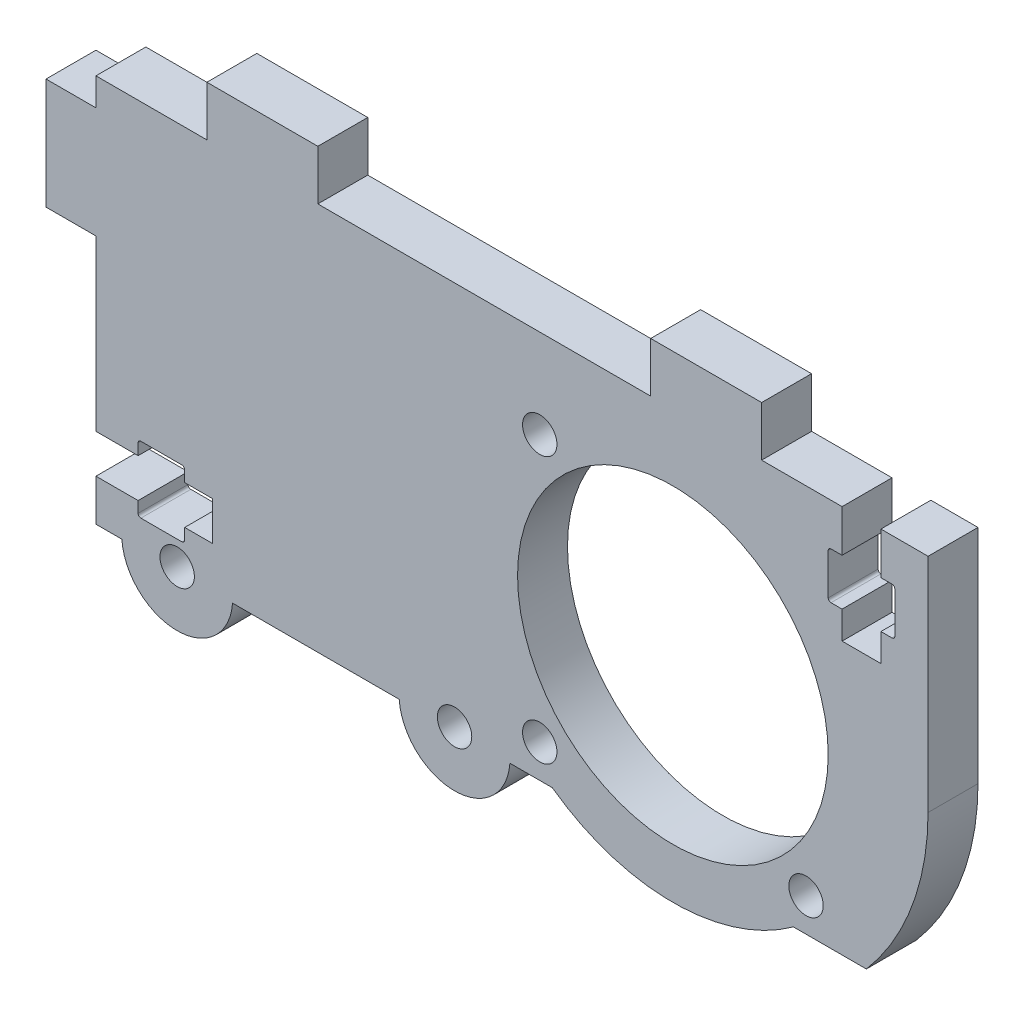
SolidWorks part; units mm, degrees
ref_plane "Front Plane" through (0, 0, 0) normal (0, 0, 1) x (1, 0, 0)
ref_plane "Top Plane" through (0, 0, 0) normal (0, 1, 0) x (1, 0, 0)
ref_plane "Right Plane" through (0, 0, 0) normal (1, 0, 0) x (0, 0, -1)
sketch "Sketch1" plane through (0, 0, 0) normal (0, 0, 1) x (1, 0, 0)
  line L0 (0, 0) -> (0, -35)
  line L1 (0, -35) -> (75, -35)
  line L2 (75, -35) -> (75, 0)
  line L3 (75, 0) -> (0, 0)
  dimension "D1" = 75
  dimension "D2" = 35
extrude "MainShape" add sketch "Sketch1" along normal blind 4.5
sketch "Sketch2" plane through (0, 0, 4.5) normal (0, 0, 1) x (1, 0, 0)
  line L0 (0, -2.5) -> (-4.5, -2.5)
  line L1 (0, 0) -> (0, -35) construction
  line L2 (-4.5, -2.5) -> (-4.5, -12.5)
  line L3 (-4.5, -12.5) -> (0, -12.5)
  line L4 (0, -12.5) -> (0, -2.5)
  line L5 (-4.5, -7.5) -> (0, -7.5) construction
  dimension "D1" = 10
  dimension "D2" = 4.5
  dimension "D3" = 7.5
extrude "RearTab" add sketch "Sketch2" against normal through all
sketch "Sketch3" plane through (0, 0, 4.5) normal (0, 0, 1) x (1, 0, 0)
  line L0 (75, 0) -> (0, 0) construction
  line L1 (10, 0) -> (20, 0)
  line L2 (10, 0) -> (10, 4.5)
  line L3 (10, 4.5) -> (20, 4.5)
  line L4 (20, 0) -> (20, 4.5)
  line L5 (15, 4.5) -> (15, 0) construction
  line L6 (50, 0) -> (60, 0)
  line L7 (50, 0) -> (50, 4.5)
  line L8 (50, 4.5) -> (60, 4.5)
  line L9 (60, 0) -> (60, 4.5)
  line L10 (55, 4.5) -> (55, 0) construction
  dimension "D1" = 4.5
  dimension "D2" = 10
  dimension "D3" = 40
  dimension "D4" = 15
extrude "Boss-Extrude3" add sketch "Sketch3" against normal through all
sketch "Sketch4" plane through (0, 0, 4.5) normal (0, 0, 1) x (1, 0, 0)
  line L0 (69, 0) -> (69, -10.5) construction
  line L1 (75, 0) -> (60, 0) construction
  line L2 (70.75, -10.5) -> (67.25, -10.5) construction
  line L3 (67.25, -10.5) -> (67.25, 0) construction
  line L4 (67.25, 0) -> (67.25, -3.8)
  line L5 (67.25, -3.8) -> (66.25, -3.8)
  line L6 (66, -4.05) -> (66, -7.75)
  line L7 (66.25, -8) -> (67.25, -8)
  line L8 (67.25, -8) -> (67.25, -10.5)
  line L9 (67.25, -10.5) -> (70.75, -10.5)
  line L10 (67.25, 0) -> (70.75, 0)
  line L11 (70.75, -10.5) -> (70.75, 0) construction
  line L12 (70.75, -8) -> (70.75, -10.5)
  line L13 (71.75, -8) -> (70.75, -8)
  line L14 (72, -4.05) -> (72, -7.75)
  line L15 (70.75, -3.8) -> (71.75, -3.8)
  line L16 (70.75, 0) -> (70.75, -3.8)
  arc A0 (66, -7.75) -> (66.25, -8) centre (66.25, -7.75) ccw
  arc A1 (66.25, -3.8) -> (66, -4.05) centre (66.25, -4.05) ccw
  arc A2 (71.75, -3.8) -> (72, -4.05) centre (71.75, -4.05) cw
  arc A3 (72, -7.75) -> (71.75, -8) centre (71.75, -7.75) cw
  point P13 (66, -8)
  point P16 (66, -3.8)
  point P27 (72, -3.8)
  point P28 (72, -8)
  dimension "D7" = 0.25
  dimension "D1" = 10.5
  dimension "D2" = 1.75
  dimension "D3" = 4.2
  dimension "D4" = 3
  dimension "D5" = 8
  dimension "D6" = 69
extrude "Cut-Extrude1" cut sketch "Sketch4" against normal through all
sketch "Sketch5" plane through (0, 0, 4.5) normal (0, 0, 1) x (1, 0, 0)
  line L0 (45.0208, 0) -> (45.0208, 4.5) construction
  line L1 (42.5416, 0) -> (47.5, 0)
  line L2 (42.5416, 0) -> (42.5416, -5.18)
  line L3 (42.5416, -5.18) -> (47.5, -5.18)
  line L4 (47.5, 0) -> (47.5, -5.18)
  line L5 (42.5416, 0) -> (47.5, -5.18) construction
  line L6 (42.5416, -5.18) -> (47.5, 0) construction
  line L7 (42, -4.18) -> (48, -4.18) construction
  line L8 (50, 0) -> (20, 0) construction
  line L9 (48, -4.18) -> (48, -1.18) construction
  line L10 (48, -2.68) -> (58, -2.68) construction
  line L11 (48, -4.18) -> (48, -1.18) construction
  line L12 (58, -1.18) -> (58, -4.18) construction
  line L13 (53, -2.68) -> (53, 0) construction
  line L14 (0, 0) -> (19.5, 0) construction
  line L15 (63.4584, -5.18) -> (58.5, 0) construction
  line L16 (63.4584, 0) -> (58.5, -5.18) construction
  line L17 (58.5, 0) -> (58.5, -5.18)
  line L18 (63.4584, -5.18) -> (58.5, -5.18)
  line L19 (63.4584, 0) -> (63.4584, -5.18)
  line L20 (63.4584, 0) -> (58.5, 0)
  line L21 (42.5416, -5.18) -> (47.5, 0) construction
  point P0 (45.0208, -2.59)
  point P27 (60.9792, -2.59)
  dimension "D1" = 1
  dimension "D2" = 0
  dimension "D3" = 0.5
extrude "Cut-Extrude2" [suppressed] cut sketch "Sketch5" against normal through all
sketch "Sketch6" plane through (0, 0, 4.5) normal (0, 0, 1) x (1, 0, 0)
  line L0 (52, -20) -> (40, -8) construction
  line L2 (52, -34) -> (52, -6) construction
  line L3 (52, -20) -> (38, -20) construction
  line L4 (52, -20) -> (64, -8) construction
  line L5 (52, -20) -> (64, -32) construction
  line L6 (52, -20) -> (40, -32) construction
  circle A0 centre (52, -20) radius 14
  circle A1 centre (40, -8) radius 1.55
  circle A3 centre (64, -32) radius 1.55
  circle A4 centre (40, -32) radius 1.55
  dimension "D1" = 28
  dimension "D4" = 3.1
  dimension "D2" = 52
  dimension "D3" = 20
  dimension "D5" = 12
  dimension "D6" = 45
extrude "Cut-Extrude3" cut sketch "Sketch6" against normal through all
sketch "Sketch7" plane through (0, 0, 4.5) normal (0, 0, 1) x (1, 0, 0)
  line L0 (0, -35) -> (62.8633, -35)
  arc A0 (41.1367, -35) -> (62.8633, -35) centre (52, -20) ccw
  circle A1 centre (52, -20) radius 14 construction
  circle A2 centre (64, -32) radius 1.55 construction
extrude "Boss-Extrude4" add sketch "Sketch7" against normal through all contours L0 A0 region at (52, -36.4204, 4.5)
sketch "Sketch8" [suppressed] plane through (0, 0, 4.5) normal (0, 0, 1) x (1, 0, 0)
  line L1 (0, -35) -> (39.1367, -35) construction
  line L18 (15, -35) -> (15, -9.316) construction
  line L19 (6.3379, -28.8128) -> (15, -37.4749) construction
  line L20 (8.8128, -26.3379) -> (17.4749, -35) construction
  line L21 (6.3379, -28.8128) -> (8.8128, -26.3379) construction
  line L22 (15, -35) -> (7.5754, -27.5754) construction
  line L23 (15, -37.4749) -> (11.0756, -33.5504)
  line L24 (11.0756, -33.5504) -> (10.1917, -34.4343)
  line L25 (10.1917, -34.4343) -> (7.2218, -31.4645)
  line L26 (7.2218, -31.4645) -> (8.1057, -30.5806)
  line L27 (8.1057, -30.5806) -> (6.3379, -28.8128)
  line L28 (15, -37.4749) -> (15, -35)
  line L29 (17.4749, -35) -> (15, -35)
  line L30 (8.8128, -26.3379) -> (6.3379, -28.8128)
  line L31 (10.5806, -28.1057) -> (8.8128, -26.3379)
  line L32 (11.4645, -27.2218) -> (10.5806, -28.1057)
  line L33 (14.4343, -30.1917) -> (11.4645, -27.2218)
  line L34 (13.5504, -31.0756) -> (14.4343, -30.1917)
  line L35 (17.4749, -35) -> (13.5504, -31.0756)
  dimension "D7" = 15
extrude "Cut-Extrude4" [suppressed] cut sketch "Sketch8" against normal through all
sketch "Sketch10" [suppressed] plane through (0, 0, 4.5) normal (0, 0, 1) x (1, 0, 0)
  line L0 (17.4749, -35) -> (21.7175, -30.7574)
  line L1 (21.7175, -30.7574) -> (25.253, -34.2929)
  line L2 (25.253, -34.2929) -> (24.5459, -35)
  line L3 (17.4749, -35) -> (39.1367, -35) construction
  line L4 (24.5459, -35) -> (17.4749, -35)
  line L5 (17.4749, -35) -> (13.5504, -31.0756) construction
  dimension "D1" = 5
  dimension "D2" = 6
extrude "Cut-Extrude6" [suppressed] cut sketch "Sketch10" against normal through all
sketch "Sketch12" plane through (0, 0, 4.5) normal (0, 0, 1) x (1, 0, 0)
  line L0 (7.3224, -34.6526) -> (32.3224, -34.6526) construction
  circle A0 centre (32.3224, -34.6526) radius 5
  circle A1 centre (7.3224, -34.6526) radius 5
  dimension "D1" = 10
  dimension "D2" = 10
  dimension "D3" = 25
  dimension "D4" = 34.6526
  dimension "D5" = 7.3224
extrude "Boss-Extrude5" add sketch "Sketch12" against normal through all
sketch "Sketch11" plane through (0, 0, 4.5) normal (0, 0, 1) x (1, 0, 0)
  line L0 (0, -29.5) -> (10.5, -29.5) construction
  line L1 (0, -12.5) -> (0, -35) construction
  line L2 (10.5, -31.25) -> (10.5, -27.75) construction
  line L3 (10.5, -27.75) -> (0, -27.75) construction
  line L4 (0, -31.25) -> (0, -27.75)
  line L5 (0, -27.75) -> (3.8, -27.75)
  line L6 (3.8, -27.75) -> (3.8, -26.75)
  line L7 (4.05, -26.5) -> (7.75, -26.5)
  line L8 (8, -26.75) -> (8, -27.75)
  line L9 (8, -27.75) -> (10.5, -27.75)
  line L10 (10.5, -27.75) -> (10.5, -31.25)
  line L11 (10.5, -31.25) -> (0, -31.25) construction
  line L12 (8, -31.25) -> (10.5, -31.25)
  line L13 (8, -32.25) -> (8, -31.25)
  line L14 (4.05, -32.5) -> (7.75, -32.5)
  line L15 (3.8, -31.25) -> (3.8, -32.25)
  line L16 (0, -31.25) -> (3.8, -31.25)
  line L17 (-4.5, -2.5) -> (-4.5, -12.5) construction
  arc A0 (7.75, -26.5) -> (8, -26.75) centre (7.75, -26.75) cw
  arc A1 (3.8, -26.75) -> (4.05, -26.5) centre (4.05, -26.75) cw
  arc A2 (3.8, -32.25) -> (4.05, -32.5) centre (4.05, -32.25) ccw
  arc A3 (7.75, -32.5) -> (8, -32.25) centre (7.75, -32.25) ccw
  point P12 (8, -26.5)
  point P15 (3.8, -26.5)
  point P26 (3.8, -32.5)
  point P27 (8, -32.5)
  point P28 (-4.5, -7.5)
  dimension "D1" = 10.5
  dimension "D2" = 1.75
  dimension "D3" = 4.2
  dimension "D4" = 3
  dimension "D5" = 8
  dimension "D6" = 0.25
  dimension "D7" = 22
extrude "Cut-Extrude7" cut sketch "Sketch11" against normal through all
sketch "Sketch13" plane through (0, 0, 4.5) normal (0, 0, 1) x (1, 0, 0)
  circle A0 centre (7.3224, -34.6526) radius 1.55
  circle A1 centre (32.3224, -34.6526) radius 1.55
  arc A2 (2.3345, -35) -> (12.3103, -35) centre (7.3224, -34.6526) ccw construction
  arc A3 (27.3345, -35) -> (37.3103, -35) centre (32.3224, -34.6526) ccw construction
  dimension "D1" = 3.1
extrude "Cut-Extrude8" cut sketch "Sketch13" against normal through all
sketch "Sketch14" plane through (0, 0, 4.5) normal (0, 0, 1) x (1, 0, 0)
  line L0 (75, -35) -> (75, 0) construction
  line L1 (69.4356, -35) -> (75, -35)
  line L2 (75, -35) -> (75, -20)
  arc A0 (69.4356, -35) -> (75, -20) centre (52, -20) ccw
  circle A1 centre (52, -20) radius 14 construction
extrude "SmoothEdge" cut sketch "Sketch14" against normal through all
equation "\"X-ROD-SPACING\"=45"
equation "\"Y-ROD-SPACING\"=75"
equation "\"Z-ROD-SPACING\"=17.5"
equation "\"Y-BED-OFFSET\"=2"
equation "\"Y-BED-ROD-INSET\"=3.5"
equation "\"Y-BED-SCREW-SPACING\"=209"
equation "\"Y-BED-SCREW-CUTOUT-SLOT-HEIGHT\"=2"
equation "\"T-SLOT-NUT-FILLET-RADIUS\"=0.25"
equation "\"T-SLOT-SCREW-SHAFT-RADIUS\"=1.75"
equation "\"T-SLOT-SCREW-SHAFT-CUTOUT-LENGTH\"=10.5"
equation "\"T-SLOT-NUT-DEPTH\"=4.2"
equation "\"T-SLOT-NUT-WIDTH\"=3"
equation "\"T-SLOT-NUT-END-DISTANCE\"=8"
equation "\"ACRYLIC-THICKNESS\"=10"
equation "\"ACRYLIC-THICKNESS2\"=4.5"
equation "\"ACRYLIC-TAB-CUTOUT-SIZE\"=\"ACRYLIC-THICKNESS\"+\"ACRYLIC-TAB-TOLERANCE\"*2"
equation "\"ACRYLIC-TAB-TOLERANCE\"=.1"
equation "\"ACRYLIC-TAB-WIDTH\"=\"ACRYLIC-THICKNESS\""
equation "\"ACRYLIC-M3-HOLE\"=3.1"
equation "\"SMOOTHROD-CAP-SCREW-DISTANCE\"=20"
equation "\"FRAME-WIDTH-INNER\"=370"
equation "\"NEMA17-HOLE-SPACING\"=31"
equation "\"NEMA17-CENTRAL-CUTOUT\"=22.5"
equation "\"Z-BRACKET-REACH\"=55"
equation "\"Z-ROD-INSET\"=16"
equation "\"TOP-BRACKET-SPACING\"=40"
equation "\"SMOOTHROD-X-LENGTH\"=350"
equation "\"SMOOTHROD-Y-LENGTH\"=350"
equation "\"SMOOTHROD-Z-LENGTH\"=350"
equation "\"SMOOTHROD-TIGHTENING-HEADROOM\"=.25"
equation "\"LEADSCREW-Z-LENGTH\"=300"
equation "\"SCREW-LENGTH-FRAME\"=\"ACRYLIC-THICKNESS\" + 10"
equation "\"SCREW-LENGTH-MOTOR\"=\"ACRYLIC-THICKNESS\" + 5"
equation "\"SCREW-LENGTH-EXTRUDER\"=28"
equation "\"SCREW-HEAD-RADIUS\"=6"
equation "\"PRINTED-M3-HOLE\"=3.5"
equation "\"PRINTED-X-SMOOTHROD-DIAMETER\"=8.2"
equation "\"PRINTED-X-SMOOTHROD-CUTOUT\"=10"
equation "\"PRINTED-X-BASE-HEIGHT\"=10"
equation "\"PRINTED-LM8UU-CUTOUT-SIZE\"=15.25"
equation "\"PRINTED-LM8UU-CUTOUT-LENGTH\"=24.5"
equation "\"PRINTED-X-IDLER-HEIGHT\"=16"
equation "\"PRINTED-M3-NUT-AF\"=6.25"
equation "\"PSU-MOUNTING-WIDTH\"=95"
equation "\"PSU-MOUNTING-HEIGHT\"=177"
equation "\"Y-BELT-TO-ROD-DISTANCE\"=20"
equation "\"SPOOL-HOLDER-ROD-SPACING\"=150"
equation "\"ACRYLIC-X-CARRIAGE-WIDTH\"=55"
equation "\"ACRYLIC-X-CARRIAGE-HEIGHT\"=75"
equation "\"ACRYLIC-X-CARRIAGE-LM8UU-CUTOUT-WIDTH\"=24.25"
equation "\"ACRYLIC-X-CARRIAGE-LM8UU-CUTOUT-HEIGHT\"=11.5"
equation "\"ACRYLIC-X-CARRIAGE-SCREW-SPACING-X\"=15"
equation "\"ACRYLIC-X-CARRIAGE-SCREW-SPACING-Y\"=33"
equation "\"ACRYLIC-X-CARRIAGE-CENTER-TAB-SPACING\"=14"
equation "\"ACRYLIC-X-CARRIAGE-EXTRUDER-OFFSET\"=26"
equation "\"ACRYLIC-X-CARRIAGE-EXTRUDER-ANGLE\"=90"
equation "\"ACRYLIC-X-CARRIAGE-EXTRUDER-SHELF-DEPTH\"=\"ACRYLIC-X-CARRIAGE-EXTRUDER-OFFSET\" + 28"
equation "\"ACRYLIC-X-CARRIAGE-EXTRUDER-BRACE-SPACING\"=23"
equation "\"ACRYLIC-X-CARRIAGE-EXTRUDER-BRACE-TAB-OFFSET\"=20"
equation "\"ACRYLIC-X-CARRIAGE-EXTRUDER-BRACE-HEIGHT\"=35"
equation "\"ACRYLIC-X-CARRIAGE-EXTRUDER-BRACE-SCREW-SPACING\"=22"
equation "\"ACRYLIC-X-CARRIAGE-DUAL-WIDTH-MULTIPLIER\"=1.65"
equation "\"ACRYLIC-X-CARRIAGE-DUAL-HOTEND-SPACING\"=42"
equation "\"ACRYLIC-X-CARRIAGE-DUAL-WIDTH\"=75"
equation "\"ACRYLIC-X-CARRIAGE-DUAL-FAN-OFFSET\"=52"
equation "\"ACRYLIC-X-CARRIAGE-DUAL-FAN-HEIGHT\"=20"
equation "\"ACRYLIC-X-CARRIAGE-DUAL-HOTEND-SEPARATION\"=36"
equation "\"ACRYLIC-X-CARRIAGE-DUAL-MOUNT-PLATE-DEPTH\"=75"
equation "\"ACRYLIC-X-CARRIAGE-DUAL-MOUNT-BRACE-WIDTH\"=33"
equation "\"ACRYLIC-X-CARRIAGE-DUAL-MOUNT-SCREW-WIDTH\"=40"
equation "\"BLOWER-FAN-WIDTH\"=15"
equation "\"D1@Sketch1\"=\"ACRYLIC-X-CARRIAGE-DUAL-MOUNT-PLATE-DEPTH\""
equation "\"D2@Sketch1\"=\"ACRYLIC-X-CARRIAGE-EXTRUDER-BRACE-HEIGHT\""
equation "\"D1@MainShape\" = \"ACRYLIC-THICKNESS2\""
equation "\"D1@Sketch2\"=\"ACRYLIC-TAB-WIDTH\""
equation "\"D2@Sketch2\"=\"ACRYLIC-THICKNESS2\""
equation "\"D1@Sketch3\"=\"ACRYLIC-THICKNESS2\""
equation "\"D2@Sketch3\"=\"ACRYLIC-TAB-WIDTH\""
equation "\"D1@Sketch4\"=\"T-SLOT-SCREW-SHAFT-CUTOUT-LENGTH\""
equation "\"D2@Sketch4\"=\"T-SLOT-SCREW-SHAFT-RADIUS\""
equation "\"D3@Sketch4\"=\"T-SLOT-NUT-DEPTH\""
equation "\"D4@Sketch4\"=\"T-SLOT-NUT-WIDTH\""
equation "\"D5@Sketch4\"=\"T-SLOT-NUT-END-DISTANCE\""
equation "\"D7@Sketch4\"=\"T-SLOT-NUT-FILLET-RADIUS\""
equation "\"D2@Sketch6\"=\"ACRYLIC-X-CARRIAGE-DUAL-FAN-OFFSET\""
equation "\"D3@Sketch6\"=\"ACRYLIC-X-CARRIAGE-DUAL-FAN-HEIGHT\""
equation "\"D4@Sketch6\"=\"ACRYLIC-M3-HOLE\""
equation "\"D1@Sketch11\"=\"T-SLOT-SCREW-SHAFT-CUTOUT-LENGTH\""
equation "\"D2@Sketch11\"=\"T-SLOT-SCREW-SHAFT-RADIUS\""
equation "\"D3@Sketch11\"=\"T-SLOT-NUT-DEPTH\""
equation "\"D4@Sketch11\"=\"T-SLOT-NUT-WIDTH\""
equation "\"D5@Sketch11\"=\"T-SLOT-NUT-END-DISTANCE\""
equation "\"D6@Sketch11\"=\"T-SLOT-NUT-FILLET-RADIUS\""
equation "\"D1@Sketch13\"=\"ACRYLIC-M3-HOLE\""
